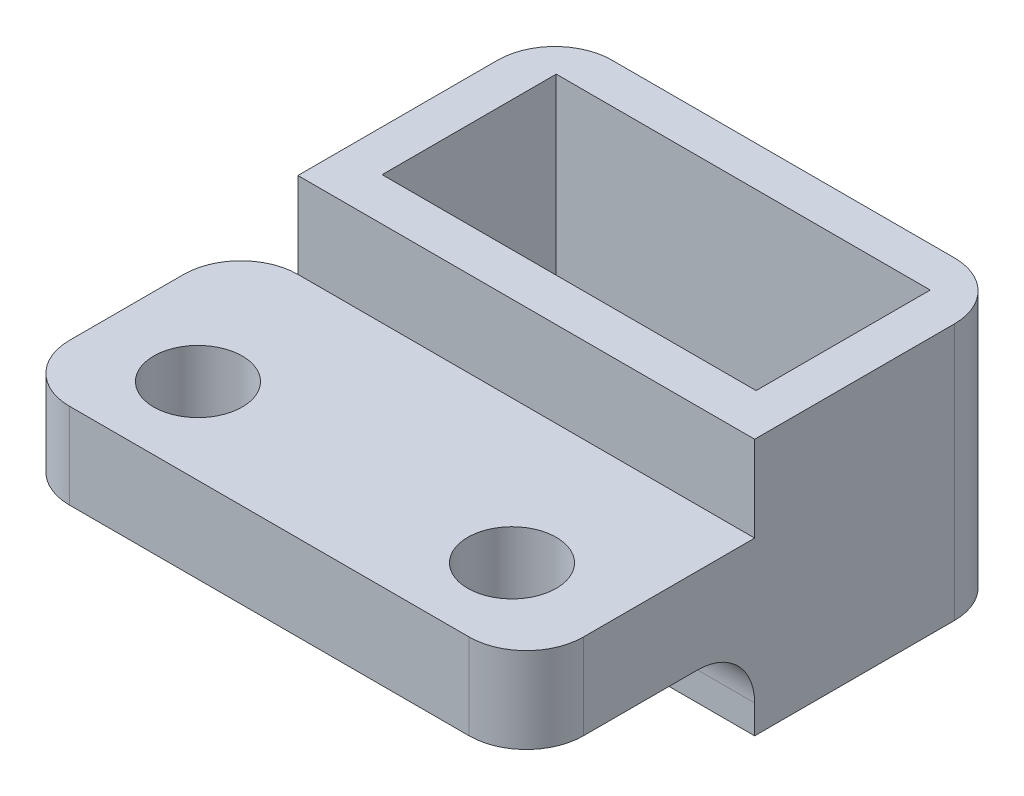
SolidWorks part; units mm, degrees
ref_plane "Alzado" through (0, 0, 0) normal (0, 0, 1) x (1, 0, 0)
ref_plane "Planta" through (0, 0, 0) normal (0, 1, 0) x (1, 0, 0)
ref_plane "Vista lateral" through (0, 0, 0) normal (1, 0, 0) x (0, 0, -1)
sketch "Croquis1" plane through (0, 0, 0) normal (0, 1, 0) x (1, 0, 0)
  line L0 (9, 18) -> (9, 0) construction
  line L1 (0, 0) -> (18, 0)
  line L2 (0, 0) -> (0, 18)
  line L3 (0, 18) -> (18, 18)
  line L4 (18, 0) -> (18, 18)
  circle A0 centre (3.5, 3) radius 1.55
  circle A1 centre (14.5, 3) radius 1.55
  point P13 (14.772, 0)
  dimension "D3" = 3.1
  dimension "D4" = 3
  dimension "D5" = 3.5
  dimension "D7" = 3
  dimension "D1" = 18
  dimension "D2" = 18
  dimension "D6" = 3.5
extrude "Saliente-Extruir1" add sketch "Croquis1" along normal blind 3
sketch "Croquis3" plane through (0, 3, 0) normal (0, 1, 0) x (1, 0, 0)
  line L0 (18, 0) -> (18, 18) construction
  line L1 (0, 18) -> (18, 18)
  line L2 (0, 18) -> (0, 8)
  line L3 (0, 8) -> (18, 8)
  line L4 (18, 18) -> (18, 8)
  dimension "D1" = 10
extrude "Saliente-Extruir3" add sketch "Croquis3" along normal blind 3
sketch "Croquis4" plane through (0, 0, 0) normal (0, -1, 0) x (1, 0, 0)
  line L1 (0, -18) -> (2, -18)
  line L2 (0, -18) -> (0, -8)
  line L3 (0, -8) -> (2, -8)
  line L4 (2, -18) -> (2, -8)
  dimension "D1" = 10
  dimension "D2" = 2
extrude "Cortar-Extruir1" cut sketch "Croquis4" against normal up to surface (6 mm away) up to face at (9, 6, -13)
sketch "Croquis7" plane through (0, 6, 0) normal (0, 1, 0) x (1, 0, 0)
  line L1 (3.45, 15.6) -> (16.55, 15.6)
  line L2 (3.45, 15.6) -> (3.45, 9.5)
  line L3 (3.45, 9.5) -> (16.55, 9.5)
  line L4 (16.55, 15.6) -> (16.55, 9.5)
  line L5 (2, 8) -> (18, 8) construction
  line L6 (2, 18) -> (2, 8) construction
  dimension "D1" = 6.1
  dimension "D2" = 13.1
  dimension "D3" = 1.5
  dimension "D4" = 1.45
extrude "Cortar-Extruir2" cut sketch "Croquis7" against normal up to surface (6 mm away) up to face at (6.6667, 0, -8.6667)
sketch "Croquis9" plane through (0, 0, 0) normal (0, -1, 0) x (1, 0, 0)
  line L0 (16.55, -15.6) -> (3.45, -15.6) construction
  line L1 (18, -18) -> (2, -18)
  line L2 (18, -18) -> (18, -8)
  line L3 (18, -8) -> (2, -8)
  line L4 (2, -18) -> (2, -8)
  line L5 (3.45, -15.6) -> (3.45, -9.5) construction
  line L6 (3.45, -9.5) -> (16.55, -9.5) construction
  line L7 (16.55, -9.5) -> (16.55, -15.6) construction
  line L8 (3.45, -9.5) -> (16.55, -9.5)
  line L9 (3.45, -15.6) -> (3.45, -9.5)
  line L10 (16.55, -15.6) -> (3.45, -15.6)
  line L11 (16.55, -9.5) -> (16.55, -15.6)
extrude "Saliente-Extruir4" add sketch "Croquis9" along normal blind 3
sketch "Croquis10" plane through (0, -3, 0) normal (0, -1, 0) x (1, 0, 0)
  line L0 (16.55, -15.6) -> (16.55, -9.5) construction
  line L1 (16.55, -9.5) -> (3.45, -9.5) construction
  line L2 (3.45, -9.5) -> (3.45, -15.6) construction
  line L3 (3.45, -15.6) -> (16.55, -15.6) construction
  line L4 (16.55, -15.6) -> (16.55, -9.5)
  line L5 (16.55, -9.5) -> (3.45, -9.5)
  line L6 (3.45, -9.5) -> (3.45, -15.6)
  line L7 (3.45, -15.6) -> (16.55, -15.6)
  line L8 (15.8, -14.85) -> (15.8, -10.25)
  line L9 (15.8, -10.25) -> (4.2, -10.25)
  line L10 (4.2, -10.25) -> (4.2, -14.85)
  line L11 (4.2, -14.85) -> (15.8, -14.85)
  dimension "D1" = 0.75
extrude "Saliente-Extruir6" add sketch "Croquis10" against normal blind 2.5
sketch "Croquis11" plane through (0, 6, 0) normal (0, 1, 0) x (1, 0, 0)
  line L0 (18, 8) -> (18, 18) construction
  line L1 (2, 18) -> (18, 18)
  line L2 (2, 18) -> (2, 17)
  line L3 (2, 17) -> (18, 17)
  line L4 (18, 18) -> (18, 17)
  dimension "D1" = 1
extrude "Cortar-Extruir4" cut sketch "Croquis11" against normal up to surface (9 mm away) up to face at (10, -3, -13)
fillet "Redondeo1" radius 2 6 edges at (18, 1.5, -17) (2, 1.5, -17) (0, 1.5, -8) (10, 0, -8) (18, 1.5, 0) (0, 1.5, 0)
